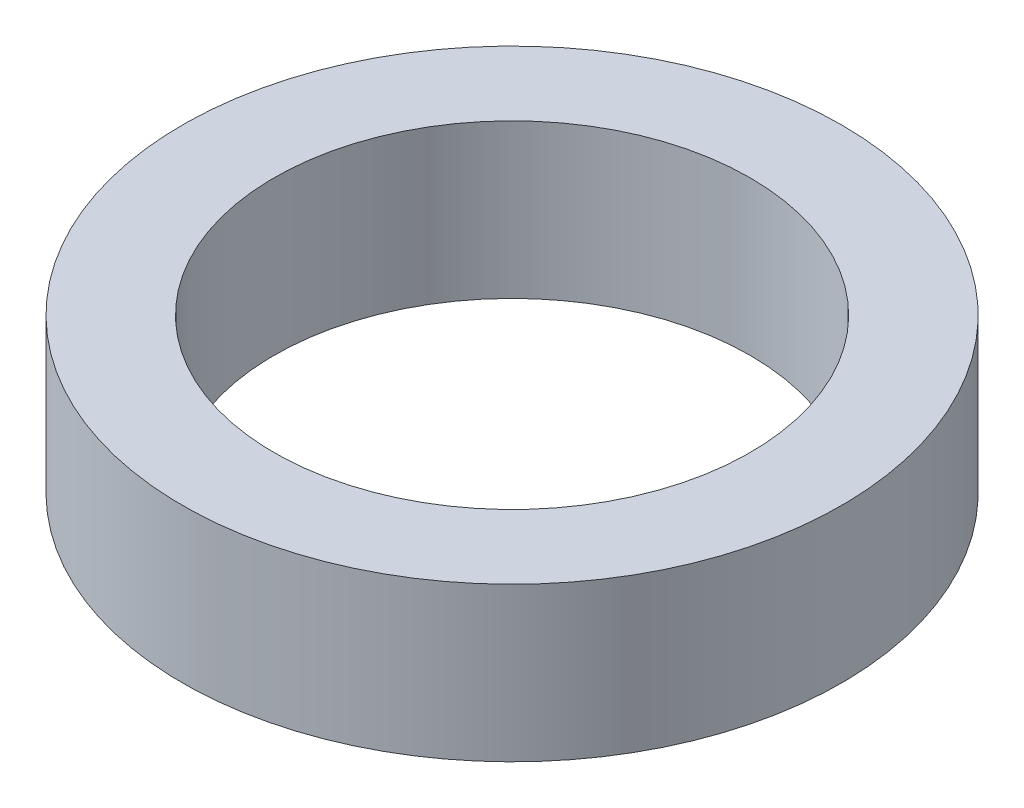
SolidWorks part; units mm, degrees
ref_plane "Front Plane" through (0, 0, 0) normal (0, 0, 1) x (1, 0, 0)
ref_plane "Top Plane" through (0, 0, 0) normal (0, 1, 0) x (1, 0, 0)
ref_plane "Right Plane" through (0, 0, 0) normal (1, 0, 0) x (0, 0, -1)
sketch "Sketch1" plane through (0, 0, 0) normal (0, 1, 0) x (1, 0, 0)
  circle A0 centre (0, 0) radius 45
  dimension "FLANGE_OD" = 90
extrude "Boss-Extrude1" add sketch "Sketch1" along normal blind 21
sketch "Sketch2" plane through (0, 0, 0) normal (0, 1, 0) x (1, 0, 0)
  circle A0 centre (0, 0) radius 32.5
  dimension "BORE_D" = 65
extrude "Cut-Extrude1" cut sketch "Sketch2" along normal through all
sketch "Sketch3" plane through (0, 21, 0) normal (0, 1, 0) x (1, 0, 0)
  circle A0 centre (0, 0) radius 20.6078 construction
  circle A1 centre (-20.6078, 0) radius 1.8102
  dimension "BOLT_D" = 3.6204
  dimension "BOLT_PCD" = 41.2156
extrude "Cut-Extrude2" cut sketch "Sketch3" against normal blind 19.862 rebuild error yes
pattern_circular "CirPattern1" count 6 over 360 rebuild error yes
